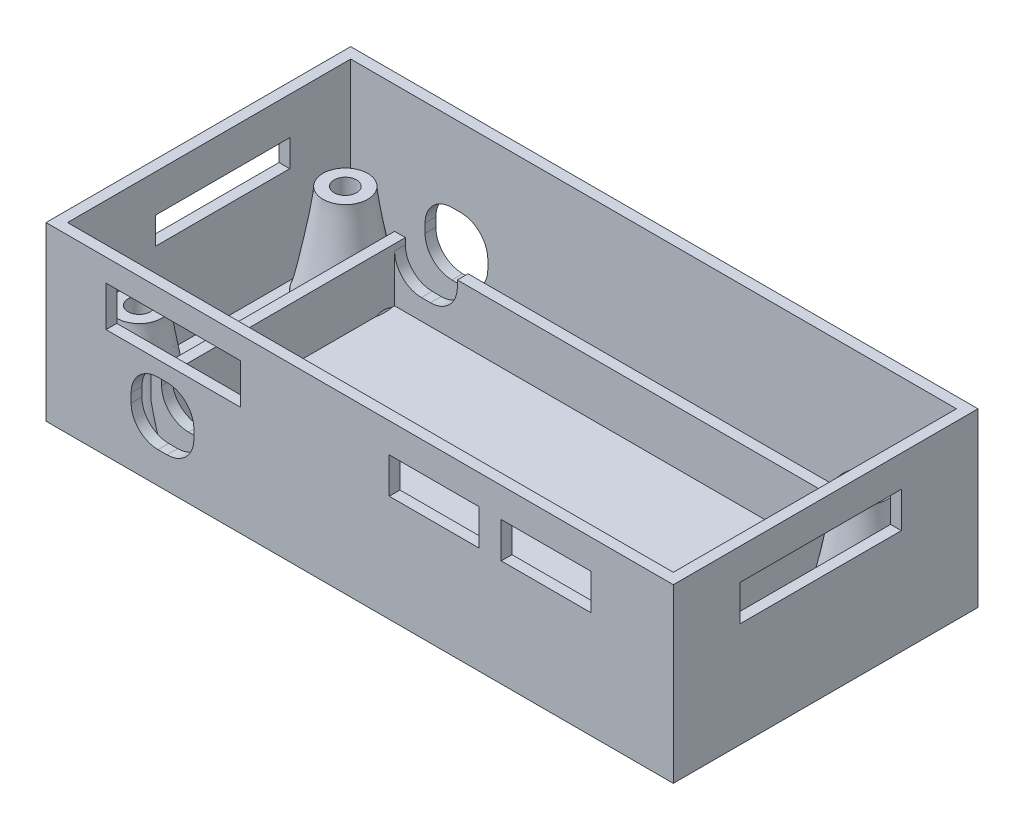
SolidWorks part; units mm, degrees
ref_plane "Front" through (0, 0, 0) normal (0, 0, 1) x (1, 0, 0)
ref_plane "Top" through (0, 0, 0) normal (0, 1, 0) x (1, 0, 0)
ref_plane "Right" through (0, 0, 0) normal (1, 0, 0) x (0, 0, -1)
sketch "Sketch1" plane through (0, 0, 0) normal (0, 1, 0) x (1, 0, 0)
  line L1 (0, 0) -> (70, 0)
  line L2 (0, 0) -> (0, -34)
  line L3 (0, -34) -> (70, -34)
  line L4 (70, 0) -> (70, -34)
  dimension "D1" = 34
  dimension "D2" = 70
extrude "Boss-Extrude1" add sketch "Sketch1" along normal blind 1.2
sketch "Sketch2" plane through (0, 1.2, 0) normal (0, 1, 0) x (1, 0, 0)
  line L0 (0, -34) -> (70, -34) construction
  line L1 (0, -34) -> (70, -34)
  line L2 (0, -34) -> (0, 0)
  line L3 (0, 0) -> (70, 0)
  line L4 (70, -34) -> (70, 0)
  line L5 (1.2, -32.8) -> (1.2, -1.2)
  line L6 (1.2, -1.2) -> (68.8, -1.2)
  line L7 (68.8, -32.8) -> (68.8, -1.2)
  line L8 (1.2, -32.8) -> (68.8, -32.8)
  dimension "D1" = 1.2
extrude "Boss-Extrude2" add sketch "Sketch2" along normal blind 18
sketch "Sketch3" plane through (0, 1.2, 0) normal (0, 1, 0) x (1, 0, 0)
  line L0 (1.2, -1.2) -> (1.2, -32.8) construction
  line L1 (1.2, -32.8) -> (68.8, -32.8) construction
  circle A0 centre (5.2, -28.8) radius 2.5
  circle A1 centre (63.2, -28.8) radius 2.5
  circle A2 centre (63.2, -5.8) radius 2.5
  circle A3 centre (5.2, -5.8) radius 2.5
  dimension "D1" = 5
  dimension "D4" = 2
  dimension "D2" = 4
  dimension "D3" = 4
  dimension "D5" = 2
extrude "Boss-Extrude3" add sketch "Sketch3" along normal blind 10
sketch "Sketch4" plane through (0, 11.2, 0) normal (0, 1, 0) x (1, 0, 0)
  circle A0 centre (5.2, -28.8) radius 1.25
  circle A1 centre (5.2, -5.8) radius 1.25
  circle A2 centre (63.2, -5.8) radius 1.25
  circle A3 centre (63.2, -28.8) radius 1.25
  dimension "D1" = 2.5
  dimension "D2" = 2.5
  dimension "D3" = 2.5
  dimension "D4" = 2.5
extrude "Cut-Extrude1" cut sketch "Sketch4" against normal through all
sketch "Sketch5" plane through (0, 0, 0) normal (-1, 0, 0) x (0, 0, 1)
  line L0 (0, 0) -> (34, 0) construction
  line L1 (8, 15) -> (23, 15)
  line L2 (8, 15) -> (8, 12)
  line L3 (8, 12) -> (23, 12)
  line L4 (23, 15) -> (23, 12)
  line L5 (34, 19.2) -> (34, 0) construction
  dimension "D1" = 3
  dimension "D2" = 15
  dimension "D3" = 12
  dimension "D4" = 11
extrude "Cut-Extrude2" cut sketch "Sketch5" against normal blind 2
sketch "Sketch7" plane through (0, 0, 32.8) normal (0, 0, -1) x (-1, 0, 0)
  line L0 (-68.8, 19.2) -> (-68.8, 1.2) construction
  line L1 (-50.8, 15.9) -> (-60.8, 15.9)
  line L2 (-50.8, 15.9) -> (-50.8, 11.9)
  line L3 (-50.8, 11.9) -> (-60.8, 11.9)
  line L4 (-60.8, 15.9) -> (-60.8, 11.9)
  line L5 (-38.3, 15.9) -> (-48.3, 15.9)
  line L6 (-38.3, 15.9) -> (-38.3, 11.9)
  line L7 (-38.3, 11.9) -> (-48.3, 11.9)
  line L8 (-48.3, 15.9) -> (-48.3, 11.9)
  line L9 (-1.2, 1.2) -> (-68.8, 1.2) construction
  dimension "D1" = 10
  dimension "D2" = 10
  dimension "D3" = 4
  dimension "D4" = 4
  dimension "D5" = 8
  dimension "D6" = 20.5
  dimension "D7" = 10.7
  dimension "D8" = 10.7
extrude "Cut-Extrude3" cut sketch "Sketch7" against normal blind 2
sketch "Sketch8" plane through (0, 0, 32.8) normal (0, 0, -1) x (-1, 0, 0)
  line L0 (-1.2, 1.2) -> (-68.8, 1.2) construction
  line L1 (-6.7, 16.7) -> (-21.7, 16.7)
  line L2 (-6.7, 16.7) -> (-6.7, 12.2)
  line L3 (-6.7, 12.2) -> (-21.7, 12.2)
  line L4 (-21.7, 16.7) -> (-21.7, 12.2)
  line L5 (-1.2, 19.2) -> (-1.2, 1.2) construction
  dimension "D1" = 15
  dimension "D2" = 4.5
  dimension "D3" = 11
  dimension "D4" = 5.5
extrude "Cut-Extrude4" cut sketch "Sketch8" against normal blind 2
sketch "Sketch9" plane through (68.8, 0, 0) normal (-1, 0, 0) x (0, 0, 1)
  line L0 (32.8, 1.2) -> (1.2, 1.2) construction
  line L1 (8.55, 15.7) -> (26.55, 15.7)
  line L2 (8.55, 15.7) -> (8.55, 11.7)
  line L3 (8.55, 11.7) -> (26.55, 11.7)
  line L4 (26.55, 15.7) -> (26.55, 11.7)
  line L5 (32.8, 19.2) -> (32.8, 1.2) construction
  dimension "D1" = 18
  dimension "D2" = 4
  dimension "D3" = 10.5
  dimension "D4" = 6.25
extrude "Cut-Extrude5" cut sketch "Sketch9" against normal blind 2
fillet "Fillet1" radius 1.9 4 edges at (63.2, 1.2, 31.3) (5.2, 1.2, 31.3) (63.2, 1.2, 8.3) (5.2, 1.2, 8.3) second distance 10 conic rho 0.1 first distance on face at (5.2, 1.2, 8.3)
sketch "Sketch10" plane through (0, 1.2, 0) normal (0, 1, 0) x (1, 0, 0)
  line L0 (68.8, -1.2) -> (1.2, -1.2) construction
  line L1 (59, -4.6) -> (9.5, -4.6)
  line L2 (59, -4.6) -> (59, -29.4)
  line L3 (59, -29.4) -> (9.5, -29.4)
  line L4 (9.5, -4.6) -> (9.5, -29.4)
  line L5 (1.2, -7.633) -> (1.2, -26.967) construction
  line L6 (60.2, -3.4) -> (8.3, -3.4)
  line L7 (8.3, -3.4) -> (8.3, -30.6)
  line L8 (60.2, -30.6) -> (8.3, -30.6)
  line L9 (60.2, -3.4) -> (60.2, -30.6)
  point P4 (0, 0)
  dimension "D1" = 49.5
  dimension "D2" = 24.8
  dimension "D3" = 3.4
  dimension "D4" = 8.3
  dimension "D5" = 1.2
extrude "Boss-Extrude4" add sketch "Sketch10" along normal blind 6
sketch "Sketch12" plane through (0, 0, 0) normal (0, 0, -1) x (-1, 0, 0)
  line L0 (-70, 0) -> (0, 0) construction
  line L1 (-9.5, 3.5) -> (-16.5, 3.5)
  line L2 (-9.5, 3.5) -> (-9.5, 10.5)
  line L3 (-9.5, 10.5) -> (-16.5, 10.5)
  line L4 (-16.5, 3.5) -> (-16.5, 10.5)
  line L5 (0, 19.2) -> (0, 0) construction
  dimension "D1" = 7
  dimension "D2" = 7
  dimension "D3" = 3.5
  dimension "D4" = 9.5
extrude "Cut-Extrude7" cut sketch "Sketch12" against normal through all
fillet "Fillet2" radius 3 10 edges at (16.5, 3.5, 30) (16.5, 3.5, 4) (9.5, 3.5, 33.4) (9.5, 3.5, 0.6) (16.5, 3.5, 33.4) (9.5, 10.5, 33.4) (16.5, 10.5, 33.4) (16.5, 10.5, 0.6) (9.5, 10.5, 0.6) (16.5, 3.5, 0.6)
